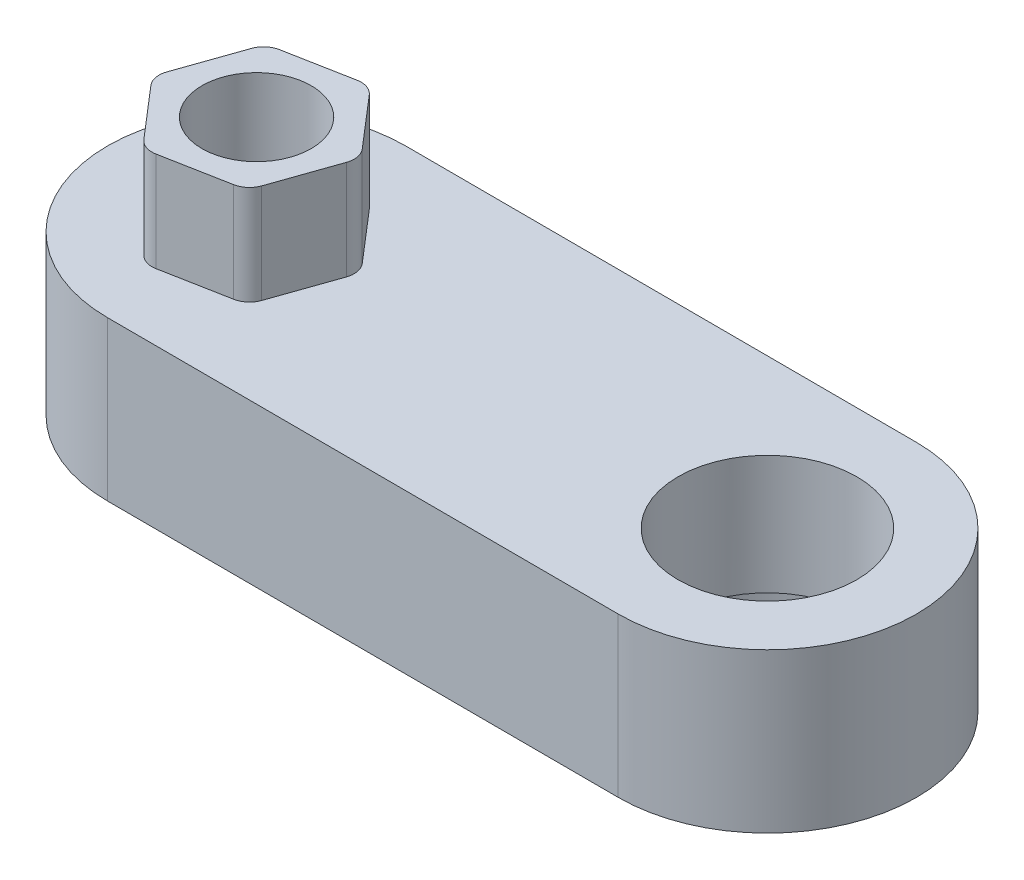
SolidWorks part; units mm, degrees
ref_plane "Front" through (0, 0, 0) normal (0, 0, 1) x (1, 0, 0)
ref_plane "Top" through (0, 0, 0) normal (0, 1, 0) x (1, 0, 0)
ref_plane "Right" through (0, 0, 0) normal (1, 0, 0) x (0, 0, -1)
sketch "Sketch1" plane through (0, 0, 0) normal (0, 1, 0) x (1, 0, 0)
  line L0 (28.1869, -18.6304) -> (2.389, -18.5643) construction
  line L1 (28.1677, -26.1304) -> (2.3697, -26.0643)
  line L2 (28.2062, -11.1304) -> (2.4082, -11.0643)
  arc A0 (28.1677, -26.1304) -> (28.2062, -11.1304) centre (28.1869, -18.6304) ccw
  arc A1 (2.4082, -11.0643) -> (2.3697, -26.0643) centre (2.389, -18.5643) ccw
  point P3 (15.288, -18.5973)
  dimension "D1" = 7.5
extrude "Boss-Extrude1" add sketch "Sketch1" along normal blind 8
sketch "Sketch2" plane through (0, 8, 0) normal (0, 1, 0) x (1, 0, 0)
  line L12 (0.9003, -22.8145) -> (5.3254, -21.9786)
  line L13 (-2.0361, -19.4002) -> (0.9003, -22.8145)
  line L14 (-0.5475, -15.15) -> (-2.0361, -19.4002)
  line L15 (3.8776, -14.3141) -> (-0.5475, -15.15)
  line L16 (6.814, -17.7284) -> (3.8776, -14.3141)
  line L17 (5.3254, -21.9786) -> (6.814, -17.7284)
  line L18 (0.9003, -22.8145) -> (5.3254, -21.9786)
  line L19 (-2.0361, -19.4002) -> (0.9003, -22.8145)
  line L20 (-0.5475, -15.15) -> (-2.0361, -19.4002)
  line L21 (3.8776, -14.3141) -> (-0.5475, -15.15)
  line L22 (6.814, -17.7284) -> (3.8776, -14.3141)
  line L23 (5.3254, -21.9786) -> (6.814, -17.7284)
  dimension "D1" = 0.2
extrude "Boss-Extrude2" add sketch "Sketch2" along normal blind 5
sketch "Sketch3" plane through (0, 13, 0) normal (0, 1, 0) x (1, 0, 0)
  circle A0 centre (2.389, -18.5643) radius 2.75
  dimension "D1" = 5.5
extrude "Cut-Extrude1" cut sketch "Sketch3" against normal through all
fillet "Fillet1" radius 1 6 edges at (-0.5475, 10.5, 15.15) (3.8776, 10.5, 14.3141) (6.814, 10.5, 17.7284) (-2.0361, 10.5, 19.4002) (0.9003, 10.5, 22.8145) (5.3254, 10.5, 21.9786)
sketch "Sketch4" plane through (0, 0, 0) normal (0, -1, 0) x (1, 0, 0)
  line L13 (7.0951, 18.4386) -> (5.9881, 21.599)
  line L14 (4.6332, 14.4258) -> (6.8167, 16.9646)
  line L15 (-0.0729, 14.5515) -> (3.2175, 13.93)
  line L16 (-2.3171, 18.69) -> (-1.2102, 15.5296)
  line L17 (0.1448, 22.7028) -> (-2.0387, 20.1639)
  line L18 (4.8509, 22.577) -> (1.5604, 23.1986)
  line L19 (7.0951, 18.4386) -> (5.9881, 21.599)
  line L20 (4.6332, 14.4258) -> (6.8167, 16.9646)
  line L21 (-0.0729, 14.5515) -> (3.2175, 13.93)
  line L22 (-2.3171, 18.69) -> (-1.2102, 15.5296)
  line L23 (0.1448, 22.7028) -> (-2.0387, 20.1639)
  line L24 (4.8509, 22.577) -> (1.5604, 23.1986)
  arc A12 (5.9881, 21.599) -> (4.8509, 22.577) centre (4.5725, 21.1031) ccw
  arc A13 (6.8167, 16.9646) -> (7.0951, 18.4386) centre (5.6794, 17.9427) ccw
  arc A14 (3.2175, 13.93) -> (4.6332, 14.4258) centre (3.4959, 15.4039) ccw
  arc A15 (-1.2102, 15.5296) -> (-0.0729, 14.5515) centre (0.2055, 16.0255) ccw
  arc A16 (-2.0387, 20.1639) -> (-2.3171, 18.69) centre (-0.9015, 19.1858) ccw
  arc A17 (1.5604, 23.1986) -> (0.1448, 22.7028) centre (1.282, 21.7247) ccw
  arc A18 (5.9881, 21.599) -> (4.8509, 22.577) centre (4.5725, 21.1031) ccw
  arc A19 (6.8167, 16.9646) -> (7.0951, 18.4386) centre (5.6794, 17.9427) ccw
  arc A20 (3.2175, 13.93) -> (4.6332, 14.4258) centre (3.4959, 15.4039) ccw
  arc A21 (-1.2102, 15.5296) -> (-0.0729, 14.5515) centre (0.2055, 16.0255) ccw
  arc A22 (-2.0387, 20.1639) -> (-2.3171, 18.69) centre (-0.9015, 19.1858) ccw
  arc A23 (1.5604, 23.1986) -> (0.1448, 22.7028) centre (1.282, 21.7247) ccw
  dimension "D1" = 0.5
extrude "Cut-Extrude2" cut sketch "Sketch4" against normal blind 3
sketch "Sketch5" plane through (0, 0, 0) normal (0, -1, 0) x (1, 0, 0)
  circle A0 centre (28.1869, 18.6304) radius 6.4 construction
  circle A1 centre (28.1869, 18.6304) radius 6.4 construction
  circle A2 centre (28.1869, 18.6304) radius 6.6
  dimension "D1" = 0.2
extrude "Cut-Extrude3" cut sketch "Sketch5" against normal blind 2 contours A2
sketch "Sketch6" plane through (0, 2, 0) normal (0, -1, 0) x (1, 0, 0)
  circle A0 centre (28.1869, 18.6304) radius 4.5
  dimension "D1" = 9
extrude "Cut-Extrude4" cut sketch "Sketch6" against normal through all
sketch "Sketch7" plane through (0, 8, 0) normal (0, 1, 0) x (1, 0, 0)
  line L0 (27.9167, -28.4758) -> (27.7384, -29.4666) construction
  line L1 (38.4822, -14.6219) -> (36.6541, -14.9672) construction
  line L2 (34.6681, -13.6123) -> (34.0608, -10.3971) construction
  line L3 (11.9627, -13.5536) -> (32.8926, -9.6001) construction
  line L4 (13.1529, -30.6294) -> (10.3687, -15.8901) construction
  line L5 (16.6576, -33.0205) -> (17.7468, -32.8147) construction
  line L6 (18.2048, -32.5975) -> (25.0681, -26.8265) construction
  line L7 (27.9167, -28.4758) -> (27.7384, -29.4666)
  line L8 (38.4822, -14.6219) -> (36.6541, -14.9672)
  line L9 (34.6681, -13.6123) -> (34.0608, -10.3971)
  line L10 (11.9627, -13.5536) -> (32.8926, -9.6001)
  line L11 (13.1529, -30.6294) -> (10.3687, -15.8901)
  line L12 (16.6576, -33.0205) -> (17.7468, -32.8147)
  line L13 (18.2048, -32.5975) -> (25.0681, -26.8265)
  arc A0 (27.9167, -28.4758) -> (25.0681, -26.8265) centre (26.1943, -28.166) ccw construction
  arc A1 (27.7384, -29.4666) -> (29.0112, -30.6011) centre (28.7226, -29.6437) ccw construction
  arc A2 (29.0112, -30.6011) -> (39.6668, -15.5592) centre (24.6822, -16.2394) ccw construction
  arc A3 (39.6668, -15.5592) -> (38.4822, -14.6219) centre (38.6678, -15.6045) ccw construction
  arc A4 (34.6681, -13.6123) -> (36.6541, -14.9672) centre (36.3386, -13.2968) ccw construction
  arc A5 (34.0608, -10.3971) -> (32.8926, -9.6001) centre (33.0782, -10.5827) ccw construction
  arc A6 (11.9627, -13.5536) -> (10.3687, -15.8901) centre (12.3339, -15.5189) ccw construction
  arc A7 (13.1529, -30.6294) -> (16.6576, -33.0205) centre (16.1007, -30.0726) ccw construction
  arc A8 (17.7468, -32.8147) -> (18.2048, -32.5975) centre (17.5612, -31.8321) ccw construction
  arc A9 (27.9167, -28.4758) -> (25.0681, -26.8265) centre (26.1943, -28.166) ccw
  arc A10 (27.7384, -29.4666) -> (29.0112, -30.6011) centre (28.7226, -29.6437) ccw
  arc A11 (29.0112, -30.6011) -> (39.6668, -15.5592) centre (24.6822, -16.2394) ccw
  arc A12 (39.6668, -15.5592) -> (38.4822, -14.6219) centre (38.6678, -15.6045) ccw
  arc A13 (34.6681, -13.6123) -> (36.6541, -14.9672) centre (36.3386, -13.2968) ccw
  arc A14 (34.0608, -10.3971) -> (32.8926, -9.6001) centre (33.0782, -10.5827) ccw
  arc A15 (11.9627, -13.5536) -> (10.3687, -15.8901) centre (12.3339, -15.5189) ccw
  arc A16 (13.1529, -30.6294) -> (16.6576, -33.0205) centre (16.1007, -30.0726) ccw
  arc A17 (17.7468, -32.8147) -> (18.2048, -32.5975) centre (17.5612, -31.8321) ccw
sketch "Sketch8" plane through (0, 8, 0) normal (0, 1, 0) x (1, 0, 0)
  line L9 (29.8383, -22.4236) -> (28.0337, -29.5197)
  line L10 (32.9541, -9.8938) -> (33.1795, 10.7177)
  line L11 (33.1795, 10.7177) -> (38.5379, -14.9167)
  line L16 (16.6019, -32.7257) -> (17.6911, -32.5199)
  line L17 (10.6635, -15.8344) -> (13.4477, -30.5738)
  line L18 (32.9482, -9.8949) -> (12.0184, -13.8484)
  line L19 (34.3733, -13.668) -> (33.766, -10.4528)
  line L20 (38.5379, -14.9167) -> (36.7098, -15.262)
  line L21 (28.2119, -28.5289) -> (28.0337, -29.5197)
  line L22 (18.0117, -32.3679) -> (24.875, -26.5969)
  line L26 (34.3733, -13.668) -> (33.766, -10.4528)
  line L27 (38.5379, -14.9167) -> (36.7098, -15.262)
  line L28 (28.2119, -28.5289) -> (28.0337, -29.5197)
  line L29 (29.8383, -22.4236) -> (24.875, -26.5969)
  arc A20 (17.6911, -32.5199) -> (18.0117, -32.3679) centre (17.5612, -31.8321) ccw
  arc A21 (13.4477, -30.5738) -> (16.6019, -32.7257) centre (16.1007, -30.0726) ccw
  arc A22 (12.0184, -13.8484) -> (10.6635, -15.8344) centre (12.3339, -15.5189) ccw
  arc A23 (33.766, -10.4528) -> (32.9482, -9.8949) centre (33.0782, -10.5827) ccw
  arc A24 (34.3733, -13.668) -> (36.7098, -15.262) centre (36.3386, -13.2968) ccw
  arc A25 (39.3671, -15.5728) -> (38.5379, -14.9167) centre (38.6678, -15.6045) ccw
  arc A26 (28.9247, -30.3139) -> (39.3671, -15.5728) centre (24.6822, -16.2394) ccw
  arc A27 (28.0337, -29.5197) -> (28.9247, -30.3139) centre (28.7226, -29.6437) ccw
  arc A28 (28.2119, -28.5289) -> (24.875, -26.5969) centre (26.1943, -28.166) ccw
  arc A32 (33.766, -10.4528) -> (32.9541, -9.8938) centre (33.0782, -10.5827) ccw
  arc A33 (34.3733, -13.668) -> (36.7098, -15.262) centre (36.3386, -13.2968) ccw
  arc A37 (28.2119, -28.5289) -> (24.875, -26.5969) centre (26.1943, -28.166) ccw
  dimension "D1" = 0.3
extrude "Cut-Extrude5" [suppressed] cut sketch "Sketch8" against normal up to surface (8 mm away) up to face at (28.1869, 0, 12.0304)
fillet "Fillet2" [suppressed] radius 2
